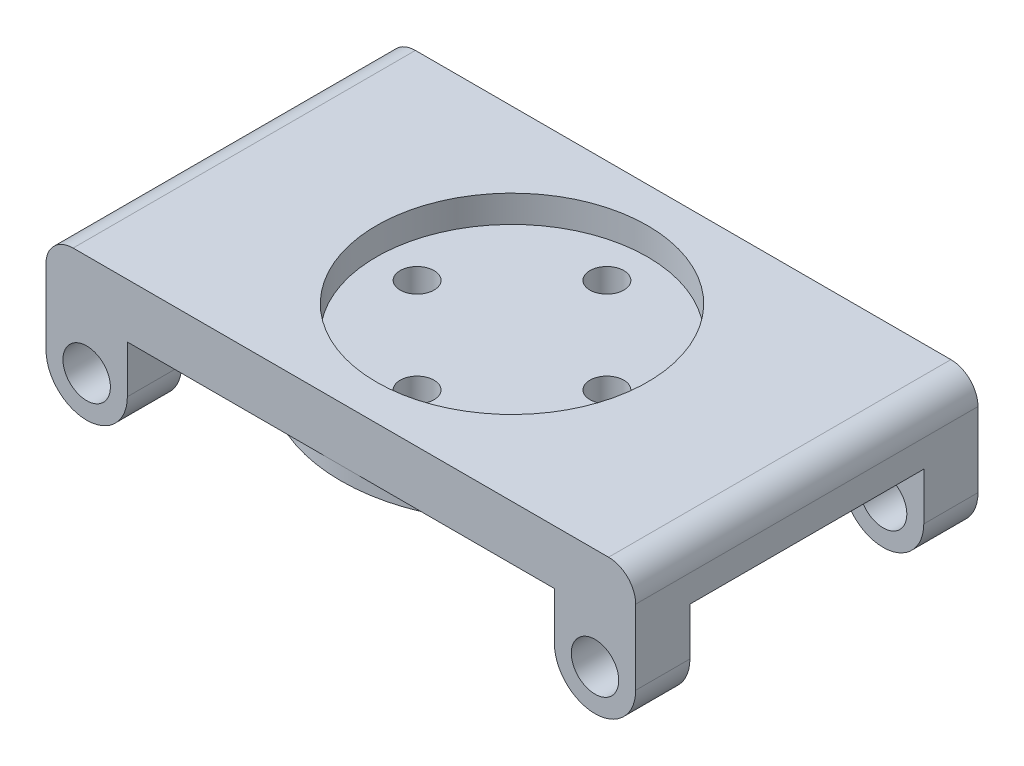
SolidWorks part; units mm, degrees
material "Esun Hard Tough Resin"
ref_plane "Front Plane" through (0, 0, 0) normal (0, 0, 1) x (1, 0, 0)
ref_plane "Top Plane" through (0, 0, 0) normal (0, 1, 0) x (1, 0, 0)
ref_plane "Right Plane" through (0, 0, 0) normal (1, 0, 0) x (0, 0, -1)
sketch "Sketch1" plane through (0, 0, 0) normal (0, 1, 0) x (1, 0, 0)
  line L1 (-21.75, -12.625) -> (21.75, -12.625)
  line L2 (-21.75, -12.625) -> (-21.75, 12.625)
  line L3 (-21.75, 12.625) -> (21.75, 12.625)
  line L4 (21.75, -12.625) -> (21.75, 12.625)
  line L5 (-21.75, -12.625) -> (21.75, 12.625) construction
  line L6 (-21.75, 12.625) -> (21.75, -12.625) construction
  point P0 (0, 0)
  dimension "D1" = 43.5
  dimension "D2" = 25.25
extrude "Boss-Extrude1" add sketch "Sketch1" along normal blind 4
sketch "Sketch5" plane through (0, 4, 0) normal (0, 1, 0) x (1, 0, 0)
  circle A0 centre (0, 0) radius 10
  dimension "D1" = 20
extrude "Cut-Extrude3" cut sketch "Sketch5" against normal blind 2
sketch "Sketch6" plane through (0, 0, 0) normal (0, -1, 0) x (1, 0, 0)
  line L0 (-21.75, 12.625) -> (21.75, 12.625) construction
  line L1 (21.75, -12.625) -> (-21.75, -12.625) construction
  circle A3 centre (0, 0) radius 12.625
extrude "Boss-Extrude3" add sketch "Sketch6" along normal blind 1
sketch "Sketch2" plane through (0, 4, 0) normal (0, 1, 0) x (1, 0, 0)
  circle A3 centre (0, 0) radius 7 construction
  circle A4 centre (0, 7) radius 1.25
  circle A5 centre (7, 0) radius 1.25
  circle A6 centre (0, -7) radius 1.25
  circle A7 centre (-7, 0) radius 1.25
  point P15 (0, 0)
  dimension "D1" = 2.5
  dimension "D2" = 14
  dimension "D3" = 4
extrude "Cut-Extrude4" cut sketch "Sketch2" against normal through all
sketch "Sketch4" plane through (0, 0, 12.625) normal (0, 0, 1) x (1, 0, 0)
  line L1 (-21.75, 0) -> (-15.75, 0)
  line L2 (-21.75, 0) -> (-21.75, -3.5)
  line L5 (0, 0) -> (0, 4) construction
  line L6 (-21.75, 4) -> (21.75, 4) construction
  line L8 (21.75, 0) -> (21.75, -3.5)
  line L9 (21.75, 0) -> (15.75, 0)
  line L11 (-21.75, 0) -> (0, 0)
  line L12 (15.75, 0) -> (21.75, 0)
  line L13 (-15.75, -3.5) -> (-15.75, 0)
  line L14 (15.75, -3.5) -> (15.75, 0)
  arc A0 (-21.75, -3.5) -> (-15.75, -3.5) centre (-18.75, -3.5) ccw
  circle A1 centre (-18.75, -3.5) radius 1.75
  circle A2 centre (18.75, -3.5) radius 1.75
  arc A3 (21.75, -3.5) -> (15.75, -3.5) centre (18.75, -3.5) cw
  line M13 (-21.75, 0) -> (0, 0)
  dimension "D2" = 3
  dimension "D4" = 3.5
  dimension "D5" = 3.5
extrude "Boss-Extrude2" add sketch "Sketch4" against normal blind 4 contours A0 L2 A1 M13 | A3 L8 A2 M13 region at (-18.75, -0.0885, 12.625) region at (21.6615, -1.75, 12.625)
mirror "Mirror1" about plane through (0, 0, 0) normal (0, 0, 1) of "Boss-Extrude2"
fillet "Fillet1" radius 2 2 edges at (21.75, 4, 0) (-21.75, 4, 0)
